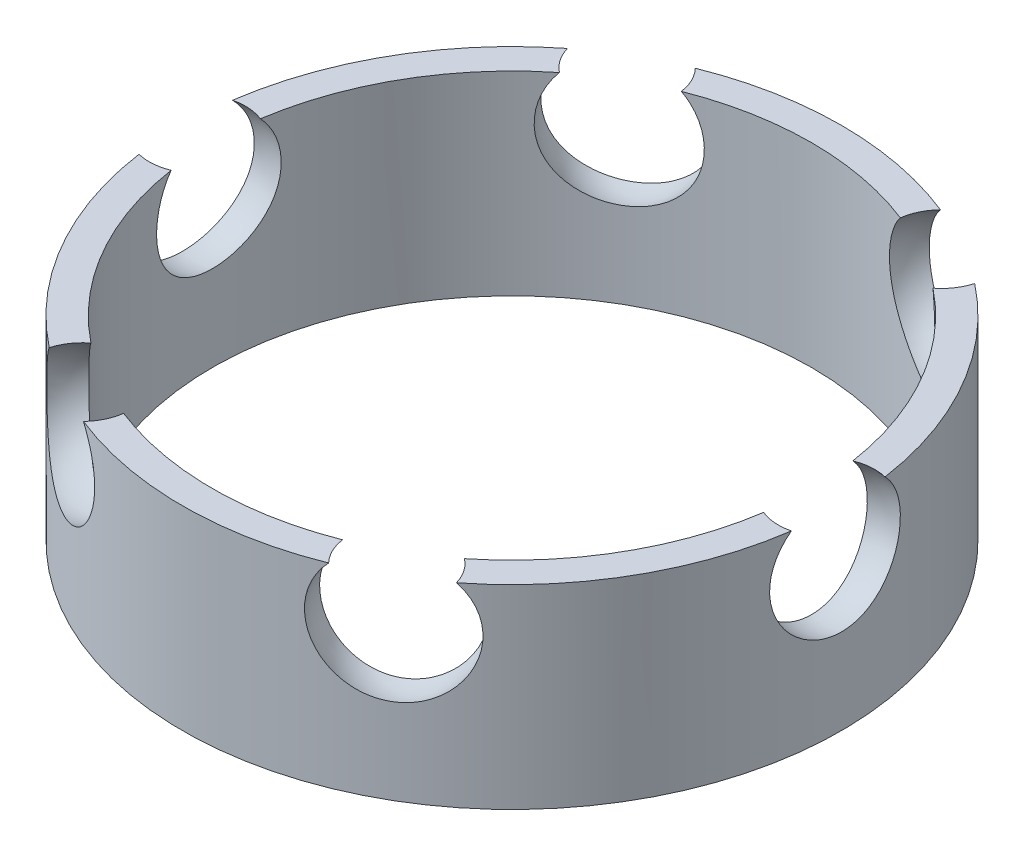
SolidWorks part; units mm, degrees
ref_plane "Front Plane" through (0, 0, 0) normal (0, 0, 1) x (1, 0, 0)
ref_plane "Top Plane" through (0, 0, 0) normal (0, 1, 0) x (1, 0, 0)
ref_plane "Right Plane" through (0, 0, 0) normal (1, 0, 0) x (0, 0, -1)
sketch "Sketch2" plane through (0, 0, 0) normal (0, 0, 1) x (1, 0, 0)
  line L0 (0, 0) -> (0, 19.8196) construction
  line L1 (0, 0) -> (10.5, 0) construction
  line L2 (8.9444, 1.5556) -> (9.5, 2.1113)
  line L3 (10.5, 0) -> (10.5, 10.5941) construction
  line L4 (9.5, 2.1113) -> (9.5, 5.5)
  line L5 (9.5, 5.5) -> (5, 5.5)
  line L6 (5, 5.5) -> (5, -5.5)
  line L7 (12.0556, 1.5556) -> (11.5, 2.1113)
  line L8 (11.5, 2.1113) -> (11.5, 5.5)
  line L9 (11.5, 5.5) -> (16, 5.5)
  line L10 (16, 5.5) -> (16, -5.5)
  line L11 (12.0556, -1.5556) -> (11.5, -2.1113)
  line L12 (8.9444, -1.5556) -> (9.5, -2.1113)
  line L13 (11.5, -5.5) -> (16, -5.5)
  line L14 (11.5, -2.1113) -> (11.5, -5.5)
  line L15 (9.5, -2.1113) -> (9.5, -5.5)
  line L16 (9.5, -5.5) -> (5, -5.5)
  line L17 (16, 0) -> (18.4, 0) construction
  line L18 (18.4, -3.1) -> (18.4, 3.1)
  line L19 (18.4, 3.1) -> (16, 5.5)
  line L20 (18.4, -3.1) -> (16, -5.5)
  line L26 (5, 5.5) -> (2.5, 5.5)
  line L27 (5, 5.5) -> (5, -5.5)
  line L28 (5, -5.5) -> (2.5, -5.5)
  line L29 (2.5, 5.5) -> (2.5, -5.5)
  arc A0 (8.9444, -1.5556) -> (8.9444, 1.5556) centre (10.5, 0) cw
  circle A1 centre (10.5, 0) radius 2 construction
  arc A2 (12.0556, -1.5556) -> (12.0556, 1.5556) centre (10.5, 0) ccw
  point P22 (16, 0)
  point P25 (5, 0)
  point P30 (18.4, 0)
  dimension "D1" = 45
  dimension "D2" = 2.2
  dimension "D3" = 4
  dimension "D4" = 2
  dimension "D5" = 6.2
  dimension "D6" = 45
  dimension "D7" = 11
  dimension "D8" = 5
  dimension "D9" = 10.5
  dimension "D10" = 2.5
sketch "Sketch3" plane through (0, 0, 0) normal (0, 0, 1) x (1, 0, 0)
  line L1 (10, -5) -> (11, -5)
  line L2 (10, -5) -> (10, 5)
  line L3 (10, 5) -> (11, 5)
  line L4 (11, -5) -> (11, 5)
  line L5 (10, -5) -> (11, 5) construction
  line L6 (10, 5) -> (11, -5) construction
  line L7 (0, 0) -> (0, 7.9473) construction
  line L8 (0, 0) -> (0, 19.8196) construction
  point P0 (10.5, 0)
  dimension "D1" = 1
  dimension "D2" = 10
sketch "Sketch4" plane through (0, 0, 0) normal (0, 0, 1) x (1, 0, 0)
  line L0 (10, -5) -> (11, 5) construction
  line L3 (10.5, -2.2) -> (10.5, 2.2)
  circle A1 centre (10.5, 0) radius 2.2
  point P4 (10.5, 0)
  point P9 (10.5, 0)
  dimension "D1" = 4.4
revolve "Revolve3" add sketch "Sketch3" angle 360 about L7
revolve "Cut-Revolve1" cut sketch "Sketch4" angle 360 about L3 region at (11.4337, 0, 0)
pattern_circular "CirPattern1" count 6 over 360 about axis through (0, 5, 0) along (0, -1, 0) of "Cut-Revolve1"
sketch "Sketch5" plane through (0, 5, 0) normal (0, 1, 0) x (1, 0, 0)
  circle A0 centre (0, 0) radius 10
  circle A1 centre (0, 0) radius 11
extrude "Cut-Extrude1" cut sketch "Sketch5" against normal blind 3.5
